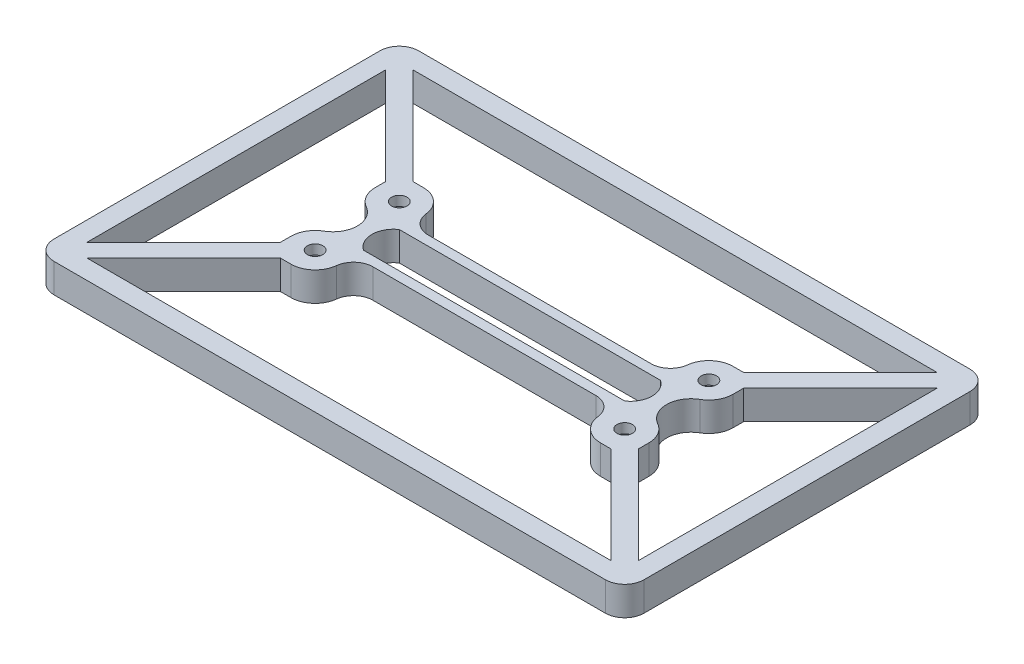
SolidWorks part; units mm, degrees
ref_plane "Alzado" through (0, 0, 0) normal (0, 0, 1) x (1, 0, 0)
ref_plane "Planta" through (0, 0, 0) normal (0, 1, 0) x (1, 0, 0)
ref_plane "Vista lateral" through (0, 0, 0) normal (1, 0, 0) x (0, 0, -1)
sketch "Croquis1" plane through (0, 0, 0) normal (0, 1, 0) x (1, 0, 0)
  line L0 (37, -13.7) -> (57, -33.7) construction
  line L1 (-32, -8.7) -> (32, -8.7) construction
  line L2 (-32, -8.7) -> (-32, 8.7) construction
  line L3 (-32, 8.7) -> (32, 8.7) construction
  line L4 (32, -8.7) -> (32, 8.7) construction
  line L5 (-32, -8.7) -> (32, 8.7) construction
  line L6 (-32, 8.7) -> (32, -8.7) construction
  line L7 (-27, 3.7) -> (27, 3.7)
  line L8 (-27, 3.7) -> (-27, -3.7) construction
  line L9 (-27, -3.7) -> (27, -3.7)
  line L10 (27, 3.7) -> (27, -3.7) construction
  line L11 (-27, 3.7) -> (27, -3.7) construction
  line L12 (-27, -3.7) -> (27, 3.7) construction
  line L13 (-37, 13.7) -> (37, 13.7)
  line L14 (-37, 13.7) -> (-37, -13.7)
  line L15 (-37, -13.7) -> (37, -13.7)
  line L16 (37, 13.7) -> (37, -13.7)
  line L17 (-37, 13.7) -> (37, -13.7) construction
  line L18 (-37, -13.7) -> (37, 13.7) construction
  line L19 (-57, 33.7) -> (57, 33.7)
  line L20 (-57, 33.7) -> (-57, -33.7)
  line L21 (-57, -33.7) -> (57, -33.7)
  line L22 (57, 33.7) -> (57, -33.7)
  line L23 (-57, 33.7) -> (57, -33.7) construction
  line L24 (-57, -33.7) -> (57, 33.7) construction
  line L25 (-27, 0) -> (-37, 0) construction
  line L26 (-32, 8.7) -> (-32, 0) construction
  line L27 (-27, 3.7) -> (-27, 13.7) construction
  line L28 (-32, 8.7) -> (-27, 8.7) construction
  line L29 (-57, -33.7) -> (-37, -13.7) construction
  line L30 (-37, 13.7) -> (-57, 33.7) construction
  line L31 (37, 13.7) -> (57, 33.7) construction
  line L32 (-34.1716, 13.7) -> (-54.1716, 33.7)
  line L33 (-37, 10.8716) -> (-57, 30.8716)
  line L34 (-35.5858, 15.1142) -> (-55.5858, 35.1142) construction
  line L35 (-38.4142, 12.2858) -> (-58.4142, 32.2858) construction
  line L36 (34.1716, -13.7) -> (54.1716, -33.7)
  line L37 (-54.1716, -33.7) -> (-34.1716, -13.7)
  line L38 (37, 10.8716) -> (57, 30.8716)
  line L39 (37, -10.8716) -> (57, -30.8716)
  line L40 (-57, -30.8716) -> (-37, -10.8716)
  line L41 (34.1716, 13.7) -> (54.1716, 33.7)
  line L42 (-58.4142, -32.2858) -> (-38.4142, -12.2858) construction
  line L43 (-55.5858, -35.1142) -> (-35.5858, -15.1142) construction
  line L44 (35.5858, -15.1142) -> (55.5858, -35.1142) construction
  line L45 (38.4142, -12.2858) -> (58.4142, -32.2858) construction
  line L46 (35.5858, 15.1142) -> (55.5858, 35.1142) construction
  line L47 (38.4142, 12.2858) -> (58.4142, 32.2858) construction
  line L48 (-57, 37.7) -> (57, 37.7)
  line L49 (61, 33.7) -> (61, -33.7)
  line L50 (-57, -37.7) -> (57, -37.7)
  line L51 (-61, 33.7) -> (-61, -33.7)
  line L52 (0, 13.7) -> (0, -13.7) construction
  line L53 (32, 8.7) -> (32, 13.7) construction
  line L54 (0, 3.7) -> (0, 5.7) construction
  line L55 (27, 5.7) -> (-27, 5.7)
  line L56 (-27, 5.7) -> (-27, 8.7)
  line L57 (27, 8.7) -> (27, 5.7)
  line L58 (27, -8.7) -> (27, -5.7)
  line L59 (27, -5.7) -> (-27, -5.7)
  line L60 (-27, -5.7) -> (-27, -8.7)
  line L61 (-61, 37.7) -> (61, 37.7) construction
  line L62 (61, 37.7) -> (61, -37.7) construction
  line L63 (-61, -37.7) -> (61, -37.7) construction
  line L64 (-61, 37.7) -> (-61, -37.7) construction
  circle A0 centre (-32, 8.7) radius 1.6
  circle A1 centre (32, 8.7) radius 1.6
  circle A2 centre (32, -8.7) radius 1.6
  circle A3 centre (-32, -8.7) radius 1.6
  circle A4 centre (-32, 8.7) radius 4
  circle A5 centre (32, 8.7) radius 4
  circle A6 centre (32, -8.7) radius 4
  circle A7 centre (-32, -8.7) radius 4
  arc A8 (-37, 8.7) -> (-34.4914, 4.3649) centre (-32, 8.7) ccw
  arc A9 (-34.4914, -4.3649) -> (-37, -8.7) centre (-32, -8.7) ccw
  arc A10 (-34.4914, -4.3649) -> (-34.4914, 4.3649) centre (-37, 0) ccw
  arc A11 (-27, -3.7) -> (-27, 3.7) centre (-24.4913, 0) cw
  arc A12 (27, -3.7) -> (27, 3.7) centre (24.4913, 0) ccw
  arc A13 (34.4914, -4.3649) -> (37, -8.7) centre (32, -8.7) cw
  arc A14 (34.4914, -4.3649) -> (34.4914, 4.3649) centre (37, 0) cw
  arc A15 (37, 8.7) -> (34.4914, 4.3649) centre (32, 8.7) cw
  arc A16 (-27, 8.7) -> (-32, 13.7) centre (-32, 8.7) ccw
  arc A17 (32, 13.7) -> (27, 8.7) centre (32, 8.7) ccw
  arc A18 (32, -13.7) -> (27, -8.7) centre (32, -8.7) cw
  arc A19 (-27, -8.7) -> (-32, -13.7) centre (-32, -8.7) cw
  arc A20 (57, 37.7) -> (61, 33.7) centre (57, 33.7) cw
  arc A21 (61, -33.7) -> (57, -37.7) centre (57, -33.7) cw
  arc A22 (-57, -37.7) -> (-61, -33.7) centre (-57, -33.7) cw
  arc A23 (-57, 37.7) -> (-61, 33.7) centre (-57, 33.7) ccw
  point P0 (0, 0)
  point P14 (0, 0)
  point P19 (0, 0)
  point P24 (0, 0)
  point P29 (37, 0)
  point P92 (0, 5.7)
  dimension "D3" = 3.2
  dimension "D4" = 8
  dimension "D15" = 4
  dimension "D1" = 64
  dimension "D2" = 17.4
  dimension "D5" = 10
  dimension "D6" = 10
  dimension "D7" = 20
  dimension "D8" = 20
  dimension "D14" = 2
  dimension "D9" = 2
  dimension "D10" = 2
  dimension "D11" = 2
  dimension "D12" = 2
  dimension "D13" = 4
extrude "Saliente-Extruir1" add sketch "Croquis1" along normal blind 6 contours L48 L51 L50 L49 L19 L22 L21 L20 | L40 L20 L21 L37 L15 L14 | L33 L14 L13 L32 L19 L20 | L41 L13 L16 L38 L22 L19 | L39 L16 L15 L36 L21 L22 | L16 L13 L14 L15 A7 A6 A5 A4 L7 L10 L9 L8 | A5 A1 | A6 A2 | A7 A3 | A4 A0 region at (-46.2929, 0, -22.9929) region at (-35.5858, 0, -12.9109) region at (46.2929, 0, -22.9929) region at (-46.2929, 0, 22.9929) region at (46.2929, 0, 22.9929) region at (0, 0, -36.2658) region at (-35.8869, 0, -8.7) region at (28.1131, 0, -8.7) region at (28.1131, 0, 8.7) region at (-35.8869, 0, 8.7)
extrude "Cortar-Extruir1" cut sketch "Croquis1<3>" along normal blind 4 contours A7 A3 | A4 A0 | A5 A1 | A6 A2 region at (-35.8869, 0, -8.7) region at (28.1131, 0, -8.7) region at (28.1131, 0, 8.7) region at (-35.8869, 0, 8.7)
sketch "Croquis1<3>" plane through (0, 0, 0) normal (0, 1, 0) x (1, 0, 0) same geometry as "Croquis1"
fillet "Redondeo1" radius 4 4 edges at (27, 3, -5.7) (27, 3, 5.7) (-27, 3, -5.7) (-27, 3, 5.7)
